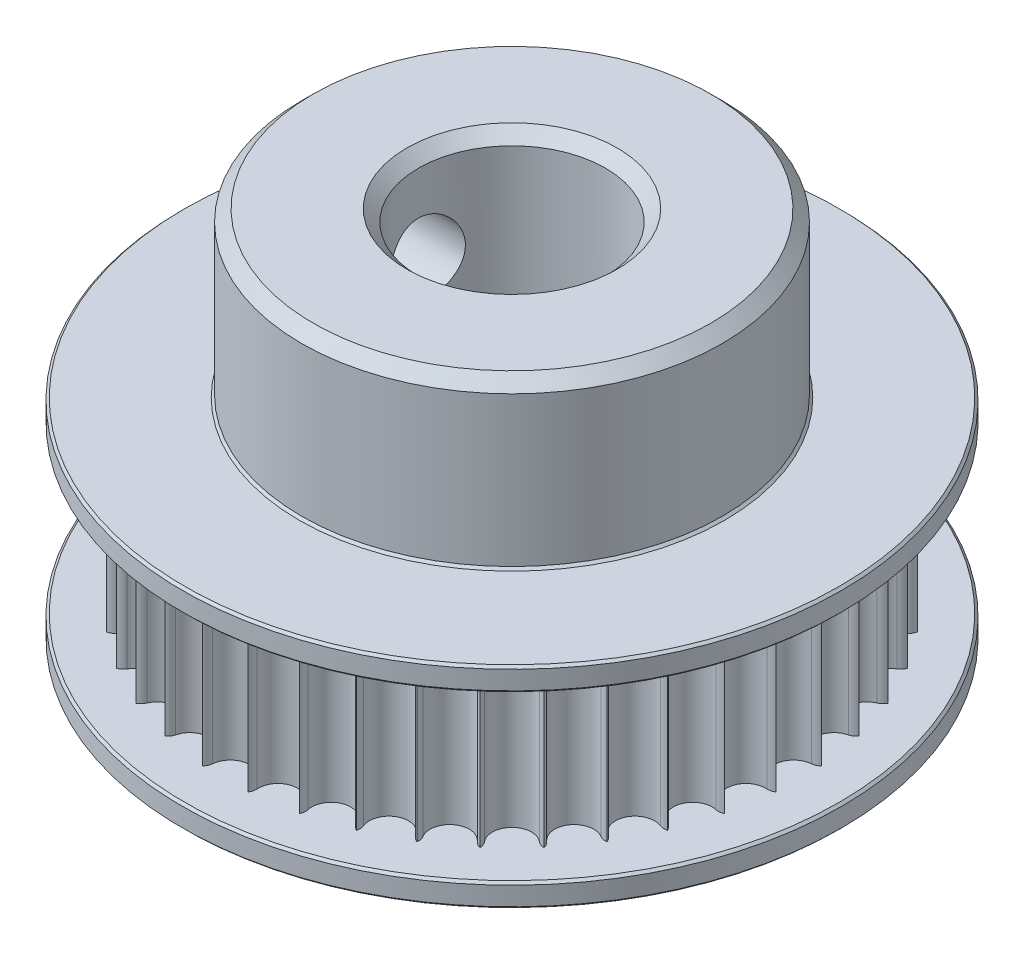
SolidWorks part; units mm, degrees
ref_plane "Front plan" through (0, 0, 0) normal (0, 0, 1) x (1, 0, 0)
ref_plane "Top plan" through (0, 0, 0) normal (0, 1, 0) x (1, 0, 0)
ref_plane "Right plan" through (0, 0, 0) normal (1, 0, 0) x (0, 0, -1)
sketch "Skica2" plane through (0, 0, 0) normal (0, 0, 1) x (1, 0, 0)
  line L0 (9, 8.5) -> (4, 8.5)
  line L1 (4, 8.5) -> (4, -8.5)
  line L2 (4, -8.5) -> (6.11, -8.5)
  line L3 (0, -8.5) -> (0, 8.5) construction
  line L4 (0, 8.5) -> (4, 8.5)
  line L5 (0, -8.5) -> (4, -8.5)
  line L6 (6.11, -8.5) -> (6.11, -7.5)
  line L7 (14.1, 0.5) -> (12.5, 0.5)
  line L8 (12.5, 0.5) -> (12.5, -6.5)
  line L9 (14.1, 0.5) -> (14.1, 1.5)
  line L12 (14.1, -7.5) -> (6.11, -7.5)
  line L13 (14.1, 1.5) -> (9, 1.5)
  line L14 (14.1, -7.5) -> (14.1, -6.5)
  line L15 (12.5, -6.5) -> (14.1, -6.5)
  line L16 (9, 1.5) -> (9, 8.5)
  point P6 (10.105, -7.5)
  point P7 (0, 0)
  dimension "D2" = 1
  dimension "D6" = 28.2
  dimension "D3" = 25
  dimension "D1" = 8
  dimension "D8" = 17
  dimension "D4" = 1
  dimension "D7" = 18
  dimension "D9" = 7
revolve "Revolute" add sketch "Skica2" angle 360 about L3 region at (7.8063, -0.6933, 0)
sketch "Sketch2" plane through (0, 0.5, 0) normal (0, -1, 0) x (1, 0, 0)
  line L0 (0, 0) -> (0, 12.0464) construction
  line L1 (0, 0) -> (4.215, 11.7679) construction
  line L3 (0, 0) -> (-2.1557, 12.3127) construction
  circle A1 centre (0, 0) radius 11.2105 construction
  circle A2 centre (0, 0) radius 12 construction
  arc A3 (-0.8326, 11.9711) -> (0.8326, 11.9711) centre (0, 12.0464) ccw
  arc A7 (-1.386, 12.4229) -> (-2.1557, 12.3127) centre (0, 0) ccw
  arc A8 (0, 13.9436) -> (2.1557, 12.3127) centre (0.592, 12.486) cw
  circle A9 centre (0, 0) radius 12.5 construction
  arc A10 (1.386, 12.4229) -> (2.1557, 12.3127) centre (0, 0) cw
  arc A11 (1.386, 12.4229) -> (0.8326, 11.9711) centre (1.3305, 11.926) ccw
  arc A12 (0, 13.9436) -> (-2.1557, 12.3127) centre (-0.592, 12.486) ccw
  arc A13 (-1.386, 12.4229) -> (-0.8326, 11.9711) centre (-1.3305, 11.926) cw
  point P0 (0.8326, 11.926)
  dimension "D2" = 1
  dimension "D4" = 0.836
  dimension "D6" = 25
  dimension "D3" = 1.5733
  dimension "D1" = 0.5
extrude "Cut-Extrude3" cut sketch "Sketch2" along normal up to surface (7 mm away) up to face at (14.1, -6.5, 0)
pattern_circular "CirPattern1" count 40 over 360 about axis through (0, -8.5, 0) along (0, -1, 0) of "Cut-Extrude3"
sketch "Sketch3" plane through (0, 0, 0) normal (1, 0, 0) x (0, 0, -1)
  line L0 (0, 8.5) -> (0, 0.5) construction
  line L1 (4, 8.5) -> (-4, 8.5) construction
  circle A0 centre (0, 4.5) radius 1.65
  dimension "D1" = 3.3
extrude "Cut-Extrude2" cut sketch "Sketch3" against normal up to next
chamfer "Chamfer1" distance 1 angle 45 1 edges at (6.11, -7.5, 0)
chamfer "Chamfer2" distance 0.5 angle 45 2 edges at (9, 8.5, 0) (4, 8.5, 0)
chamfer "Chamfer3" distance 0.1 angle 45 5 edges at (14.1, -7.5, 0) (14.1, -6.5, 0) (14.1, 0.5, 0) (14.1, 1.5, 0) (9, 1.5, 0)
equation "\"`\"=2"
equation "\"D6@Sketch2\"= \"D3@Skica2\""
